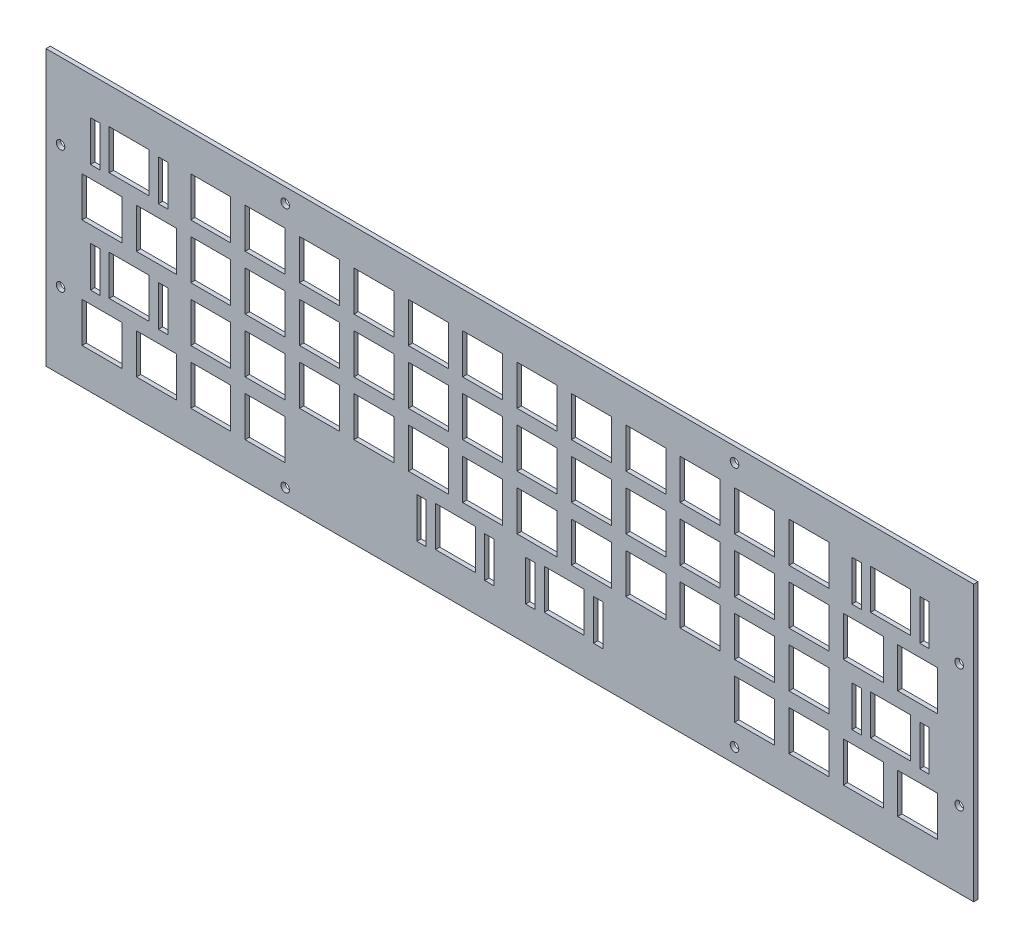
SolidWorks part; units mm, degrees
material "6061 Alloy"
ref_plane "Front Plane" through (0, 0, 0) normal (0, 0, 1) x (1, 0, 0)
ref_plane "Top Plane" through (0, 0, 0) normal (0, 1, 0) x (1, 0, 0)
ref_plane "Right Plane" through (0, 0, 0) normal (1, 0, 0) x (0, 0, -1)
sketch "Model" plane through (0, 0, 0) normal (0, 0, 1) x (1, 0, 0)
  line L0 (0.0937, 96.2808) -> (324.895, 96.2808)
  line L1 (324.895, 96.2808) -> (324.895, 0.0799)
  line L2 (324.895, 0.0799) -> (0.0937, 0.0799)
  line L3 (0.0937, 0.0799) -> (0.0937, 96.2808)
  line L4 (129.892, 26.056) -> (133.194, 26.056)
  line L5 (133.194, 26.056) -> (133.194, 11.8553)
  line L6 (133.194, 11.8553) -> (129.892, 11.8553)
  line L7 (129.892, 11.8553) -> (129.892, 26.056)
  line L8 (153.694, 26.056) -> (156.994, 26.056)
  line L9 (156.994, 26.056) -> (156.994, 11.8553)
  line L10 (156.994, 11.8553) -> (153.694, 11.8553)
  line L11 (153.694, 11.8553) -> (153.694, 26.056)
  line L12 (167.992, 26.056) -> (171.294, 26.056)
  line L13 (171.294, 26.056) -> (171.294, 11.8553)
  line L14 (171.294, 11.8553) -> (167.992, 11.8553)
  line L15 (167.992, 11.8553) -> (167.992, 26.056)
  line L16 (191.794, 26.056) -> (195.094, 26.056)
  line L17 (195.094, 26.056) -> (195.094, 11.8553)
  line L18 (195.094, 11.8553) -> (191.794, 11.8553)
  line L19 (191.794, 11.8553) -> (191.794, 26.056)
  line L20 (12.6187, 26.6058) -> (26.6182, 26.6058)
  line L21 (26.6182, 26.6058) -> (26.6182, 12.6063)
  line L22 (26.6182, 12.6063) -> (12.6187, 12.6063)
  line L23 (12.6187, 12.6063) -> (12.6187, 26.6058)
  line L24 (31.6687, 26.6058) -> (45.6681, 26.6058)
  line L25 (45.6681, 26.6058) -> (45.6681, 12.6063)
  line L26 (45.6681, 12.6063) -> (31.6687, 12.6063)
  line L27 (31.6687, 12.6063) -> (31.6687, 26.6058)
  line L28 (50.7189, 26.6058) -> (64.7181, 26.6058)
  line L29 (64.7181, 26.6058) -> (64.7181, 12.6063)
  line L30 (64.7181, 12.6063) -> (50.7189, 12.6063)
  line L31 (50.7189, 12.6063) -> (50.7189, 26.6058)
  line L32 (69.7689, 26.6058) -> (83.7681, 26.6058)
  line L33 (83.7681, 26.6058) -> (83.7681, 12.6063)
  line L34 (83.7681, 12.6063) -> (69.7689, 12.6063)
  line L35 (69.7689, 12.6063) -> (69.7689, 26.6058)
  line L36 (136.444, 26.6058) -> (150.443, 26.6058)
  line L37 (150.443, 26.6058) -> (150.443, 12.6063)
  line L38 (150.443, 12.6063) -> (136.444, 12.6063)
  line L39 (136.444, 12.6063) -> (136.444, 26.6058)
  line L40 (174.544, 26.6058) -> (188.543, 26.6058)
  line L41 (188.543, 26.6058) -> (188.543, 12.6063)
  line L42 (188.543, 12.6063) -> (174.544, 12.6063)
  line L43 (174.544, 12.6063) -> (174.544, 26.6058)
  line L44 (241.219, 26.6058) -> (255.218, 26.6058)
  line L45 (255.218, 26.6058) -> (255.218, 12.6063)
  line L46 (255.218, 12.6063) -> (241.219, 12.6063)
  line L47 (241.219, 12.6063) -> (241.219, 26.6058)
  line L48 (260.269, 26.6058) -> (274.268, 26.6058)
  line L49 (274.268, 26.6058) -> (274.268, 12.6063)
  line L50 (274.268, 12.6063) -> (260.269, 12.6063)
  line L51 (260.269, 12.6063) -> (260.269, 26.6058)
  line L52 (279.319, 26.6058) -> (293.318, 26.6058)
  line L53 (293.318, 26.6058) -> (293.318, 12.6063)
  line L54 (293.318, 12.6063) -> (279.319, 12.6063)
  line L55 (279.319, 12.6063) -> (279.319, 26.6058)
  line L56 (298.369, 26.6058) -> (312.368, 26.6058)
  line L57 (312.368, 26.6058) -> (312.368, 12.6063)
  line L58 (312.368, 12.6063) -> (298.369, 12.6063)
  line L59 (298.369, 12.6063) -> (298.369, 26.6058)
  line L60 (15.5925, 45.1058) -> (18.8929, 45.1058)
  line L61 (18.8929, 45.1058) -> (18.8929, 30.9053)
  line L62 (18.8929, 30.9053) -> (15.5925, 30.9053)
  line L63 (15.5925, 30.9053) -> (15.5925, 45.1058)
  line L64 (39.394, 45.1058) -> (42.6932, 45.1058)
  line L65 (42.6932, 45.1058) -> (42.6932, 30.9053)
  line L66 (42.6932, 30.9053) -> (39.394, 30.9053)
  line L67 (39.394, 30.9053) -> (39.394, 45.1058)
  line L68 (282.294, 45.1058) -> (285.594, 45.1058)
  line L69 (285.594, 45.1058) -> (285.594, 30.9053)
  line L70 (285.594, 30.9053) -> (282.294, 30.9053)
  line L71 (282.294, 30.9053) -> (282.294, 45.1058)
  line L72 (306.094, 45.1058) -> (309.394, 45.1058)
  line L73 (309.394, 45.1058) -> (309.394, 30.9053)
  line L74 (309.394, 30.9053) -> (306.094, 30.9053)
  line L75 (306.094, 30.9053) -> (306.094, 45.1058)
  line L76 (22.1423, 45.6558) -> (36.1431, 45.6558)
  line L77 (36.1431, 45.6558) -> (36.1431, 31.6563)
  line L78 (36.1431, 31.6563) -> (22.1423, 31.6563)
  line L79 (22.1423, 31.6563) -> (22.1423, 45.6558)
  line L80 (50.7189, 45.6558) -> (64.7181, 45.6558)
  line L81 (64.7181, 45.6558) -> (64.7181, 31.6563)
  line L82 (64.7181, 31.6563) -> (50.7189, 31.6563)
  line L83 (50.7189, 31.6563) -> (50.7189, 45.6558)
  line L84 (69.7689, 45.6558) -> (83.7681, 45.6558)
  line L85 (83.7681, 45.6558) -> (83.7681, 31.6563)
  line L86 (83.7681, 31.6563) -> (69.7689, 31.6563)
  line L87 (69.7689, 31.6563) -> (69.7689, 45.6558)
  line L88 (88.8189, 45.6558) -> (102.818, 45.6558)
  line L89 (102.818, 45.6558) -> (102.818, 31.6563)
  line L90 (102.818, 31.6563) -> (88.8189, 31.6563)
  line L91 (88.8189, 31.6563) -> (88.8189, 45.6558)
  line L92 (107.867, 45.6558) -> (121.868, 45.6558)
  line L93 (121.868, 45.6558) -> (121.868, 31.6563)
  line L94 (121.868, 31.6563) -> (107.867, 31.6563)
  line L95 (107.867, 31.6563) -> (107.867, 45.6558)
  line L96 (126.919, 45.6558) -> (140.918, 45.6558)
  line L97 (140.918, 45.6558) -> (140.918, 31.6563)
  line L98 (140.918, 31.6563) -> (126.919, 31.6563)
  line L99 (126.919, 31.6563) -> (126.919, 45.6558)
  line L100 (145.969, 45.6558) -> (159.968, 45.6558)
  line L101 (159.968, 45.6558) -> (159.968, 31.6563)
  line L102 (159.968, 31.6563) -> (145.969, 31.6563)
  line L103 (145.969, 31.6563) -> (145.969, 45.6558)
  line L104 (165.019, 45.6558) -> (179.018, 45.6558)
  line L105 (179.018, 45.6558) -> (179.018, 31.6563)
  line L106 (179.018, 31.6563) -> (165.019, 31.6563)
  line L107 (165.019, 31.6563) -> (165.019, 45.6558)
  line L108 (184.069, 45.6558) -> (198.068, 45.6558)
  line L109 (198.068, 45.6558) -> (198.068, 31.6563)
  line L110 (198.068, 31.6563) -> (184.069, 31.6563)
  line L111 (184.069, 31.6563) -> (184.069, 45.6558)
  line L112 (203.119, 45.6558) -> (217.118, 45.6558)
  line L113 (217.118, 45.6558) -> (217.118, 31.6563)
  line L114 (217.118, 31.6563) -> (203.119, 31.6563)
  line L115 (203.119, 31.6563) -> (203.119, 45.6558)
  line L116 (222.169, 45.6558) -> (236.168, 45.6558)
  line L117 (236.168, 45.6558) -> (236.168, 31.6563)
  line L118 (236.168, 31.6563) -> (222.169, 31.6563)
  line L119 (222.169, 31.6563) -> (222.169, 45.6558)
  line L120 (241.219, 45.6558) -> (255.218, 45.6558)
  line L121 (255.218, 45.6558) -> (255.218, 31.6563)
  line L122 (255.218, 31.6563) -> (241.219, 31.6563)
  line L123 (241.219, 31.6563) -> (241.219, 45.6558)
  line L124 (260.269, 45.6558) -> (274.268, 45.6558)
  line L125 (274.268, 45.6558) -> (274.268, 31.6563)
  line L126 (274.268, 31.6563) -> (260.269, 31.6563)
  line L127 (260.269, 31.6563) -> (260.269, 45.6558)
  line L128 (288.844, 45.6558) -> (302.843, 45.6558)
  line L129 (302.843, 45.6558) -> (302.843, 31.6563)
  line L130 (302.843, 31.6563) -> (288.844, 31.6563)
  line L131 (288.844, 31.6563) -> (288.844, 45.6558)
  line L132 (12.6187, 64.7058) -> (26.6182, 64.7058)
  line L133 (26.6182, 64.7058) -> (26.6182, 50.7062)
  line L134 (26.6182, 50.7062) -> (12.6187, 50.7062)
  line L135 (12.6187, 50.7062) -> (12.6187, 64.7058)
  line L136 (31.6687, 64.7058) -> (45.6681, 64.7058)
  line L137 (45.6681, 64.7058) -> (45.6681, 50.7062)
  line L138 (45.6681, 50.7062) -> (31.6687, 50.7062)
  line L139 (31.6687, 50.7062) -> (31.6687, 64.7058)
  line L140 (50.7189, 64.7058) -> (64.7181, 64.7058)
  line L141 (64.7181, 64.7058) -> (64.7181, 50.7062)
  line L142 (64.7181, 50.7062) -> (50.7189, 50.7062)
  line L143 (50.7189, 50.7062) -> (50.7189, 64.7058)
  line L144 (69.7689, 64.7058) -> (83.7681, 64.7058)
  line L145 (83.7681, 64.7058) -> (83.7681, 50.7062)
  line L146 (83.7681, 50.7062) -> (69.7689, 50.7062)
  line L147 (69.7689, 50.7062) -> (69.7689, 64.7058)
  line L148 (88.8189, 64.7058) -> (102.818, 64.7058)
  line L149 (102.818, 64.7058) -> (102.818, 50.7062)
  line L150 (102.818, 50.7062) -> (88.8189, 50.7062)
  line L151 (88.8189, 50.7062) -> (88.8189, 64.7058)
  line L152 (107.867, 64.7058) -> (121.868, 64.7058)
  line L153 (121.868, 64.7058) -> (121.868, 50.7062)
  line L154 (121.868, 50.7062) -> (107.867, 50.7062)
  line L155 (107.867, 50.7062) -> (107.867, 64.7058)
  line L156 (126.919, 64.7058) -> (140.918, 64.7058)
  line L157 (140.918, 64.7058) -> (140.918, 50.7062)
  line L158 (140.918, 50.7062) -> (126.919, 50.7062)
  line L159 (126.919, 50.7062) -> (126.919, 64.7058)
  line L160 (145.969, 64.7058) -> (159.968, 64.7058)
  line L161 (159.968, 64.7058) -> (159.968, 50.7062)
  line L162 (159.968, 50.7062) -> (145.969, 50.7062)
  line L163 (145.969, 50.7062) -> (145.969, 64.7058)
  line L164 (165.019, 64.7058) -> (179.018, 64.7058)
  line L165 (179.018, 64.7058) -> (179.018, 50.7062)
  line L166 (179.018, 50.7062) -> (165.019, 50.7062)
  line L167 (165.019, 50.7062) -> (165.019, 64.7058)
  line L168 (184.069, 64.7058) -> (198.068, 64.7058)
  line L169 (198.068, 64.7058) -> (198.068, 50.7062)
  line L170 (198.068, 50.7062) -> (184.069, 50.7062)
  line L171 (184.069, 50.7062) -> (184.069, 64.7058)
  line L172 (203.119, 64.7058) -> (217.118, 64.7058)
  line L173 (217.118, 64.7058) -> (217.118, 50.7062)
  line L174 (217.118, 50.7062) -> (203.119, 50.7062)
  line L175 (203.119, 50.7062) -> (203.119, 64.7058)
  line L176 (222.169, 64.7058) -> (236.168, 64.7058)
  line L177 (236.168, 64.7058) -> (236.168, 50.7062)
  line L178 (236.168, 50.7062) -> (222.169, 50.7062)
  line L179 (222.169, 50.7062) -> (222.169, 64.7058)
  line L180 (241.219, 64.7058) -> (255.218, 64.7058)
  line L181 (255.218, 64.7058) -> (255.218, 50.7062)
  line L182 (255.218, 50.7062) -> (241.219, 50.7062)
  line L183 (241.219, 50.7062) -> (241.219, 64.7058)
  line L184 (260.269, 64.7058) -> (274.268, 64.7058)
  line L185 (274.268, 64.7058) -> (274.268, 50.7062)
  line L186 (274.268, 50.7062) -> (260.269, 50.7062)
  line L187 (260.269, 50.7062) -> (260.269, 64.7058)
  line L188 (279.319, 64.7058) -> (293.318, 64.7058)
  line L189 (293.318, 64.7058) -> (293.318, 50.7062)
  line L190 (293.318, 50.7062) -> (279.319, 50.7062)
  line L191 (279.319, 50.7062) -> (279.319, 64.7058)
  line L192 (298.369, 64.7058) -> (312.368, 64.7058)
  line L193 (312.368, 64.7058) -> (312.368, 50.7062)
  line L194 (312.368, 50.7062) -> (298.369, 50.7062)
  line L195 (298.369, 50.7062) -> (298.369, 64.7058)
  line L196 (15.5925, 83.2058) -> (18.8929, 83.2058)
  line L197 (18.8929, 83.2058) -> (18.8929, 69.0051)
  line L198 (18.8929, 69.0051) -> (15.5925, 69.0051)
  line L199 (15.5925, 69.0051) -> (15.5925, 83.2058)
  line L200 (39.394, 83.2058) -> (42.6932, 83.2058)
  line L201 (42.6932, 83.2058) -> (42.6932, 69.0051)
  line L202 (42.6932, 69.0051) -> (39.394, 69.0051)
  line L203 (39.394, 69.0051) -> (39.394, 83.2058)
  line L204 (282.294, 83.2058) -> (285.594, 83.2058)
  line L205 (285.594, 83.2058) -> (285.594, 69.0051)
  line L206 (285.594, 69.0051) -> (282.294, 69.0051)
  line L207 (282.294, 69.0051) -> (282.294, 83.2058)
  line L208 (306.094, 83.2058) -> (309.394, 83.2058)
  line L209 (309.394, 83.2058) -> (309.394, 69.0051)
  line L210 (309.394, 69.0051) -> (306.094, 69.0051)
  line L211 (306.094, 69.0051) -> (306.094, 83.2058)
  line L212 (22.1423, 83.7558) -> (36.1431, 83.7558)
  line L213 (36.1431, 83.7558) -> (36.1431, 69.7562)
  line L214 (36.1431, 69.7562) -> (22.1423, 69.7562)
  line L215 (22.1423, 69.7562) -> (22.1423, 83.7558)
  line L216 (50.7189, 83.7558) -> (64.7181, 83.7558)
  line L217 (64.7181, 83.7558) -> (64.7181, 69.7562)
  line L218 (64.7181, 69.7562) -> (50.7189, 69.7562)
  line L219 (50.7189, 69.7562) -> (50.7189, 83.7558)
  line L220 (69.7689, 83.7558) -> (83.7681, 83.7558)
  line L221 (83.7681, 83.7558) -> (83.7681, 69.7562)
  line L222 (83.7681, 69.7562) -> (69.7689, 69.7562)
  line L223 (69.7689, 69.7562) -> (69.7689, 83.7558)
  line L224 (88.8189, 83.7558) -> (102.818, 83.7558)
  line L225 (102.818, 83.7558) -> (102.818, 69.7562)
  line L226 (102.818, 69.7562) -> (88.8189, 69.7562)
  line L227 (88.8189, 69.7562) -> (88.8189, 83.7558)
  line L228 (107.867, 83.7558) -> (121.868, 83.7558)
  line L229 (121.868, 83.7558) -> (121.868, 69.7562)
  line L230 (121.868, 69.7562) -> (107.867, 69.7562)
  line L231 (107.867, 69.7562) -> (107.867, 83.7558)
  line L232 (126.919, 83.7558) -> (140.918, 83.7558)
  line L233 (140.918, 83.7558) -> (140.918, 69.7562)
  line L234 (140.918, 69.7562) -> (126.919, 69.7562)
  line L235 (126.919, 69.7562) -> (126.919, 83.7558)
  line L236 (145.969, 83.7558) -> (159.968, 83.7558)
  line L237 (159.968, 83.7558) -> (159.968, 69.7562)
  line L238 (159.968, 69.7562) -> (145.969, 69.7562)
  line L239 (145.969, 69.7562) -> (145.969, 83.7558)
  line L240 (165.019, 83.7558) -> (179.018, 83.7558)
  line L241 (179.018, 83.7558) -> (179.018, 69.7562)
  line L242 (179.018, 69.7562) -> (165.019, 69.7562)
  line L243 (165.019, 69.7562) -> (165.019, 83.7558)
  line L244 (184.069, 83.7558) -> (198.068, 83.7558)
  line L245 (198.068, 83.7558) -> (198.068, 69.7562)
  line L246 (198.068, 69.7562) -> (184.069, 69.7562)
  line L247 (184.069, 69.7562) -> (184.069, 83.7558)
  line L248 (203.119, 83.7558) -> (217.118, 83.7558)
  line L249 (217.118, 83.7558) -> (217.118, 69.7562)
  line L250 (217.118, 69.7562) -> (203.119, 69.7562)
  line L251 (203.119, 69.7562) -> (203.119, 83.7558)
  line L252 (222.169, 83.7558) -> (236.168, 83.7558)
  line L253 (236.168, 83.7558) -> (236.168, 69.7562)
  line L254 (236.168, 69.7562) -> (222.169, 69.7562)
  line L255 (222.169, 69.7562) -> (222.169, 83.7558)
  line L256 (241.219, 83.7558) -> (255.218, 83.7558)
  line L257 (255.218, 83.7558) -> (255.218, 69.7562)
  line L258 (255.218, 69.7562) -> (241.219, 69.7562)
  line L259 (241.219, 69.7562) -> (241.219, 83.7558)
  line L260 (260.269, 83.7558) -> (274.268, 83.7558)
  line L261 (274.268, 83.7558) -> (274.268, 69.7562)
  line L262 (274.268, 69.7562) -> (260.269, 69.7562)
  line L263 (260.269, 69.7562) -> (260.269, 83.7558)
  line L264 (288.844, 83.7558) -> (302.843, 83.7558)
  line L265 (302.843, 83.7558) -> (302.843, 69.7562)
  line L266 (302.843, 69.7562) -> (288.844, 69.7562)
  line L267 (288.844, 69.7562) -> (288.844, 83.7558)
  line L272 (10.0937, 86.2808) -> (10.0937, 10.0799)
  line L273 (10.0937, 10.0799) -> (314.895, 10.0799)
  line L274 (314.895, 10.0799) -> (314.895, 86.2808)
  line L275 (314.895, 86.2808) -> (10.0937, 86.2808)
  point P273 (83.794, 5.0799)
  point P274 (241.1947, 91.2808)
  point P276 (10.0937, 86.2808)
  point P277 (10.0937, 10.0799)
  point P278 (314.895, 10.0799)
  point P279 (314.895, 86.2808)
  point P292 (5.0937, 58.9555)
  point P293 (319.895, 15.855)
  point P305 (5.0937, 26.6301)
  point P306 (83.794, 91.2808)
  point P307 (241.1947, 5.0799)
  point P308 (319.895, 69.7306)
extrude "Boss-Extrude2" add sketch "Model" along normal blind 1.5 contours L274 L275 L272 L273 L266 L267 L264 L265 L262 L263 L260 L261 L258 L259 L256 L257 L254 L255 L252 L253 L250 L251 L248 L249 L246 L247 L244 L245 L242 L243 L240 L241 L238 L239 L236 L237 L234 L235 L232 L233 L230 region at (162.4966, 46.1945, 0)
sketch "Sketch1" plane through (0, 0, 1.5) normal (0, 0, 1) x (1, 0, 0)
  point P0 (29.1427, 76.756)
  point P1 (143.4435, 19.606)
  point P3 (29.1427, 38.6561)
  point P4 (181.5435, 19.606)
  point P8 (229.1685, 38.6561)
  point P9 (229.1685, 57.706)
  point P10 (229.1685, 76.756)
  point P11 (210.1185, 76.756)
  point P12 (295.8435, 38.6561)
  point P13 (286.3185, 19.606)
  point P14 (286.3185, 57.706)
  point P15 (305.3685, 19.606)
  point P16 (305.3685, 57.706)
  point P17 (210.1185, 57.706)
  point P19 (210.1185, 38.6561)
  point P20 (191.0685, 38.6561)
  point P24 (191.0685, 57.706)
  point P29 (191.0685, 76.756)
  point P30 (172.0185, 76.756)
  point P36 (172.0185, 57.706)
  point P39 (172.0185, 38.6561)
  point P40 (152.9685, 38.6561)
  point P41 (152.9685, 57.706)
  point P42 (152.9685, 76.756)
  point P45 (133.9185, 76.756)
  point P46 (133.9185, 57.706)
  point P49 (133.9185, 38.6561)
  point P50 (114.8675, 38.6561)
  point P53 (114.8675, 57.706)
  point P54 (114.8675, 76.756)
  point P57 (95.8184, 76.756)
  point P61 (95.8185, 57.706)
  point P62 (95.8184, 38.6561)
  point P65 (76.7685, 38.6561)
  point P67 (76.7685, 57.706)
  point P69 (76.7685, 76.756)
  point P70 (57.7185, 76.756)
  point P73 (57.7185, 57.706)
  point P75 (57.7185, 38.6561)
  point P77 (57.7185, 19.606)
  point P80 (19.6185, 19.606)
  point P81 (38.6684, 19.606)
  point P86 (76.7685, 19.606)
  point P89 (38.6684, 57.706)
  point P90 (19.6185, 57.706)
  point P223 (295.8435, 76.756)
  point P224 (267.2685, 19.606)
  point P225 (267.2685, 38.6561)
  point P226 (267.2685, 57.706)
  point P227 (267.2685, 76.756)
  point P228 (248.2185, 76.756)
  point P229 (248.2185, 57.706)
  point P230 (248.2185, 38.6561)
  point P231 (248.2185, 19.606)
sketch "Sketch2" plane through (0, 0, 0) normal (0, 0, 1) x (1, 0, 0)
  point P0 (29.1427, 76.756)
  point P1 (143.4435, 19.606)
  point P3 (29.1427, 38.6561)
  point P4 (181.5435, 19.606)
  point P8 (229.1685, 38.6561)
  point P9 (229.1685, 57.706)
  point P10 (229.1685, 76.756)
  point P11 (210.1185, 76.756)
  point P12 (295.8435, 38.6561)
  point P13 (286.3185, 19.606)
  point P14 (286.3185, 57.706)
  point P15 (305.3685, 19.606)
  point P16 (305.3685, 57.706)
  point P17 (210.1185, 57.706)
  point P19 (210.1185, 38.6561)
  point P20 (191.0685, 38.6561)
  point P24 (191.0685, 57.706)
  point P29 (191.0685, 76.756)
  point P30 (172.0185, 76.756)
  point P36 (172.0185, 57.706)
  point P39 (172.0185, 38.6561)
  point P40 (152.9685, 38.6561)
  point P41 (152.9685, 57.706)
  point P42 (152.9685, 76.756)
  point P45 (133.9185, 76.756)
  point P46 (133.9185, 57.706)
  point P49 (133.9185, 38.6561)
  point P50 (114.8675, 38.6561)
  point P53 (114.8675, 57.706)
  point P54 (114.8675, 76.756)
  point P57 (95.8184, 76.756)
  point P61 (95.8185, 57.706)
  point P62 (95.8184, 38.6561)
  point P65 (76.7685, 38.6561)
  point P67 (76.7685, 57.706)
  point P69 (76.7685, 76.756)
  point P70 (57.7185, 76.756)
  point P73 (57.7185, 57.706)
  point P75 (57.7185, 38.6561)
  point P77 (57.7185, 19.606)
  point P80 (19.6185, 19.606)
  point P81 (38.6684, 19.606)
  point P86 (76.7685, 19.606)
  point P89 (38.6684, 57.706)
  point P90 (19.6185, 57.706)
  point P223 (295.8435, 76.756)
  point P224 (267.2685, 19.606)
  point P225 (267.2685, 38.6561)
  point P226 (267.2685, 57.706)
  point P227 (267.2685, 76.756)
  point P228 (248.2185, 76.756)
  point P229 (248.2185, 57.706)
  point P230 (248.2185, 38.6561)
  point P231 (248.2185, 19.606)
ref_axis "Axis2" through (305.3685, 19.606, 0) along (0, 0, 1)
ref_axis "Axis3" through (286.3185, 19.606, 0) along (0, 0, 1)
ref_axis "Axis4" through (295.8435, 38.6561, 0) along (0, 0, 1)
ref_axis "Axis5" through (267.2685, 38.6561, 0) along (0, 0, 1)
ref_axis "Axis6" through (286.3185, 57.706, 0) along (0, 0, 1)
ref_axis "Axis7" through (305.3685, 57.706, 0) along (0, 0, 1)
ref_axis "Axis8" through (295.8435, 76.756, 0) along (0, 0, 1)
ref_axis "Axis9" through (267.2685, 76.756, 0) along (0, 0, 1)
ref_axis "Axis10" through (248.2185, 76.756, 0) along (0, 0, 1)
ref_axis "Axis11" through (229.1685, 76.756, 0) along (0, 0, 1)
ref_axis "Axis12" through (210.1185, 76.756, 0) along (0, 0, 1)
ref_axis "Axis13" through (267.2685, 57.706, 0) along (0, 0, 1)
ref_axis "Axis14" through (248.2185, 57.706, 0) along (0, 0, 1)
ref_axis "Axis15" through (229.1685, 57.706, 0) along (0, 0, 1)
ref_axis "Axis16" through (191.0685, 76.756, 0) along (0, 0, 1)
ref_axis "Axis17" through (172.0185, 76.756, 0) along (0, 0, 1)
ref_axis "Axis18" through (152.9685, 76.756, 0) along (0, 0, 1)
ref_axis "Axis19" through (133.9185, 76.756, 0) along (0, 0, 1)
ref_axis "Axis20" through (114.8675, 76.756, 0) along (0, 0, 1)
ref_axis "Axis21" through (95.8184, 76.756, 0) along (0, 0, 1)
ref_axis "Axis22" through (76.7685, 76.756, 0) along (0, 0, 1)
ref_axis "Axis23" through (57.7185, 76.756, 0) along (0, 0, 1)
ref_axis "Axis24" through (29.1427, 76.756, 0) along (0, 0, 1)
ref_axis "Axis25" through (19.6185, 57.706, 0) along (0, 0, 1)
ref_axis "Axis26" through (38.6684, 57.706, 0) along (0, 0, 1)
ref_axis "Axis27" through (57.7185, 57.706, 0) along (0, 0, 1)
ref_axis "Axis28" through (76.7685, 57.706, 0) along (0, 0, 1)
ref_axis "Axis29" through (95.8185, 57.706, 0) along (0, 0, 1)
ref_axis "Axis30" through (114.8675, 57.706, 0) along (0, 0, 1)
ref_axis "Axis31" through (133.9185, 57.706, 0) along (0, 0, 1)
ref_axis "Axis32" through (172.0185, 57.706, 0) along (0, 0, 1)
ref_axis "Axis33" through (152.9685, 57.706, 0) along (0, 0, 1)
ref_axis "Axis34" through (191.0685, 57.706, 0) along (0, 0, 1)
ref_axis "Axis35" through (210.1185, 57.706, 0) along (0, 0, 1)
ref_axis "Axis38" through (248.2185, 38.6561, 0) along (0, 0, 1)
ref_axis "Axis39" through (229.1685, 38.6561, 0) along (0, 0, 1)
ref_axis "Axis40" through (210.1185, 38.6561, 0) along (0, 0, 1)
ref_axis "Axis41" through (191.0685, 38.6561, 0) along (0, 0, 1)
ref_axis "Axis42" through (172.0185, 38.6561, 0) along (0, 0, 1)
ref_axis "Axis43" through (152.9685, 38.6561, 0) along (0, 0, 1)
ref_axis "Axis44" through (267.2685, 19.606, 0) along (0, 0, 1)
ref_axis "Axis45" through (248.2185, 19.606, 0) along (0, 0, 1)
ref_axis "Axis46" through (181.5435, 19.606, 0) along (0, 0, 1)
ref_axis "Axis47" through (133.9185, 38.6561, 0) along (0, 0, 1)
ref_axis "Axis48" through (143.4435, 19.606, 0) along (0, 0, 1)
ref_axis "Axis49" through (114.8675, 38.6561, 0) along (0, 0, 1)
ref_axis "Axis50" through (95.8184, 38.6561, 0) along (0, 0, 1)
ref_axis "Axis51" through (76.7685, 38.6561, 0) along (0, 0, 1)
ref_axis "Axis52" through (57.7185, 38.6561, 0) along (0, 0, 1)
ref_axis "Axis53" through (29.1427, 38.6561, 0) along (0, 0, 1)
ref_axis "Axis54" through (19.6185, 19.606, 0) along (0, 0, 1)
ref_axis "Axis55" through (38.6684, 19.606, 0) along (0, 0, 1)
ref_axis "Axis56" through (57.7185, 19.606, 1.5) along (0, 0, -1)
ref_axis "Axis57" through (76.7685, 19.606, 1.5) along (0, 0, -1)
sketch "Sketch3" plane through (0, 0, 1.5) normal (0, 0, 1) x (1, 0, 0)
  line L1 (0, 0) -> (324.9887, 0)
  line L2 (0, 0) -> (0, 96.3745)
  line L3 (10.0937, 86.2808) -> (314.895, 86.2808)
  line L4 (10.0937, 86.2808) -> (10.0937, 10.0799)
  line L5 (0, 96.3745) -> (324.9887, 96.3745)
  line L6 (324.9887, 0) -> (324.9887, 96.3745)
  line L7 (10.0937, 10.0799) -> (314.895, 10.0799)
  line L8 (314.895, 86.2808) -> (314.895, 10.0799)
  point P21 (324.9887, 0)
  point P22 (324.9887, 96.3745)
  point P23 (0, 96.3745)
  point P24 (0, 0)
extrude "Boss-Extrude4" add sketch "Sketch3" against normal blind 1.5
sketch "Sketch4" plane through (0, 0, 0) normal (0, 0, 1) x (1, 0, 0)
  circle A0 centre (5.0937, 69.7306) radius 1.5
  circle A1 centre (5.0937, 26.6301) radius 1.5
  circle A2 centre (83.794, 5.0799) radius 1.5
  circle A3 centre (241.1947, 5.0799) radius 1.5
  circle A4 centre (319.895, 26.6301) radius 1.5
  circle A5 centre (319.895, 69.7306) radius 1.5
  circle A6 centre (241.1947, 91.2808) radius 1.5
  circle A7 centre (83.794, 91.2808) radius 1.5
  point P6 (5.0937, 69.7306)
  point P7 (319.895, 26.6301)
  point P273 (83.794, 5.0799)
  point P274 (241.1947, 91.2808)
  point P305 (5.0937, 26.6301)
  point P306 (83.794, 91.2808)
  point P307 (241.1947, 5.0799)
  point P308 (319.895, 69.7306)
extrude "Cut-Extrude2" cut sketch "Sketch4" along normal blind 2.54
